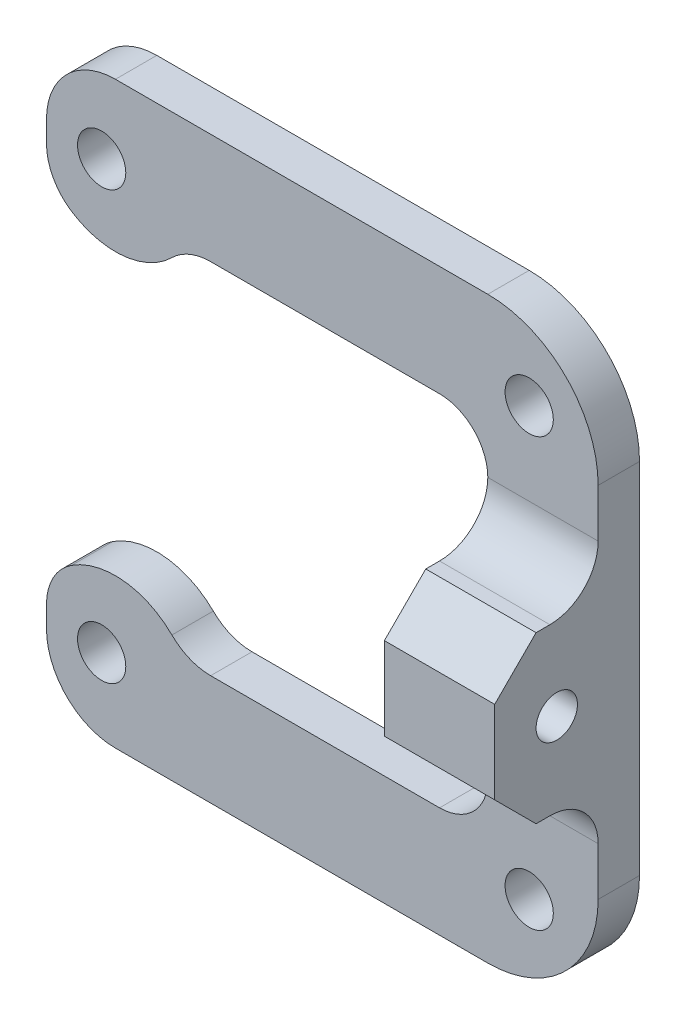
SolidWorks part; units mm, degrees
ref_plane "Front Plane" through (0, 0, 0) normal (0, 0, 1) x (1, 0, 0)
ref_plane "Top Plane" through (0, 0, 0) normal (0, 1, 0) x (1, 0, 0)
ref_plane "Right Plane" through (0, 0, 0) normal (1, 0, 0) x (0, 0, -1)
other "Graphic1"
other "Graphic (Closed) -1"
sketch "Sketch1" plane through (0, 0, 0) normal (0, 0, 1) x (1, 0, 0)
  line L0 (-20, 16) -> (-20, 14.4663)
  line L1 (-15, 21) -> (12, 21)
  line L2 (-15, -21) -> (12, -21)
  line L3 (20, 13) -> (20, -13)
  line L4 (12, 13) -> (12, -13)
  line L5 (-8.0973, -13) -> (12, -13)
  line L7 (-8.0973, 13) -> (12, 13)
  line L8 (-12, 13) -> (12, 13) construction
  line L9 (-12, -13) -> (12, -13) construction
  line L10 (-12, 13) -> (-12, -13) construction
  line L11 (-20, 16) -> (-20, 13)
  line L12 (-20, 21) -> (-20, -21) construction
  line L13 (-20, -21) -> (20, -21) construction
  line L14 (20, 21) -> (20, -21) construction
  line L15 (-20, 21) -> (20, 21) construction
  line L16 (-20, -14.4663) -> (-20, -16)
  line L17 (12, 13) -> (12, -13) construction
  arc A0 (12, -21) -> (20, -13) centre (12, -13) ccw
  arc A1 (12, 21) -> (20, 13) centre (12, 13) cw
  arc A2 (-20, -16) -> (-15, -21) centre (-15, -16) ccw
  arc A3 (-20, 16) -> (-15, 21) centre (-15, 16) cw
  arc A6 (-18.1847, 11.1155) -> (-10.9058, 11.8481) centre (-15, 16) ccw
  arc A7 (-10.9058, -11.8481) -> (-18.1847, -11.1155) centre (-15, -16) ccw
  arc A8 (-10.9058, -11.8481) -> (-8.0973, -13) centre (-8.0973, -9) ccw
  arc A9 (-8.0973, 13) -> (-10.9058, 11.8481) centre (-8.0973, 9) ccw
  arc A10 (-18.1847, 11.1155) -> (-20, 14.4663) centre (-16, 14.4663) cw
  arc A11 (-18.1847, -11.1155) -> (-20, -14.4663) centre (-16, -14.4663) ccw
  circle A12 centre (15, 15.5) radius 1.75
  circle A13 centre (15, -15.5) radius 1.75
  circle A14 centre (-16, -15.5) radius 1.75
  circle A15 centre (-16, 15.5) radius 1.75
  point P14 (20, -21)
  dimension "D6" = 8
  dimension "D1" = 5
  dimension "D9" = 4
  dimension "D12" = 3.5
  dimension "D13" = 3.5
  dimension "D18" = 3.5
  dimension "D19" = 3.5
  dimension "D2" = 21
  dimension "D3" = 21
  dimension "D4" = 20
  dimension "D7" = 12
  dimension "D10" = 5
  dimension "D11" = 5.5
  dimension "D14" = 5.5
  dimension "D15" = 5
  dimension "D16" = 4
  dimension "D17" = 5.5
  dimension "D20" = 5.5
  dimension "D21" = 4
  dimension "D5" = 8
extrude "Boss-Extrude1" add sketch "Sketch1" along normal blind 3
sketch "Sketch2" plane through (20, 0, 0) normal (1, 0, 0) x (0, 0, -1)
  line L0 (-10.5, 3) -> (-7.5, 6)
  line L1 (-7.5, 6) -> (-3, 6)
  line L2 (-3, 6) -> (-3, -6)
  line L3 (-3, -6) -> (-7.5, -6)
  line L4 (-7.5, -6) -> (-10.5, -3)
  line L5 (-10.5, -3) -> (-10.5, 3)
  line L6 (0, 0) -> (-10.5, 0) construction
  line L7 (-3, 13) -> (-3, -13) construction
  line L8 (0, 13) -> (0, -13) construction
  circle A0 centre (-6, 0) radius 1.5
  dimension "D1" = 3
  dimension "D2" = 10.5
  dimension "D3" = 12
  dimension "D4" = 6
  dimension "D5" = 6
extrude "Boss-Extrude2" add sketch "Sketch2" against normal up to surface (8 mm away) up to face at (12, 0, 1.5)
fillet "Fillet1" radius 3.5 4 edges at (16, 6, 3) (16, -6, 3) (12, -13, 1.5) (12, 13, 1.5)
sketch "Sketch3" plane through (12, 0, 0) normal (-1, 0, 0) x (0, 0, 1)
  line L1 (6, 3.1754) -> (3.25, 1.5877)
  line L2 (3.25, 1.5877) -> (3.25, -1.5877)
  line L3 (3.25, -1.5877) -> (6, -3.1754)
  line L4 (6, -3.1754) -> (8.75, -1.5877)
  line L5 (8.75, -1.5877) -> (8.75, 1.5877)
  line L6 (8.75, 1.5877) -> (6, 3.1754)
  circle A0 centre (6, 0) radius 2.75 construction
  dimension "D1" = 5.5
  dimension "D2" = 6
extrude "Cut-Extrude1" cut sketch "Sketch3" against normal blind 4
